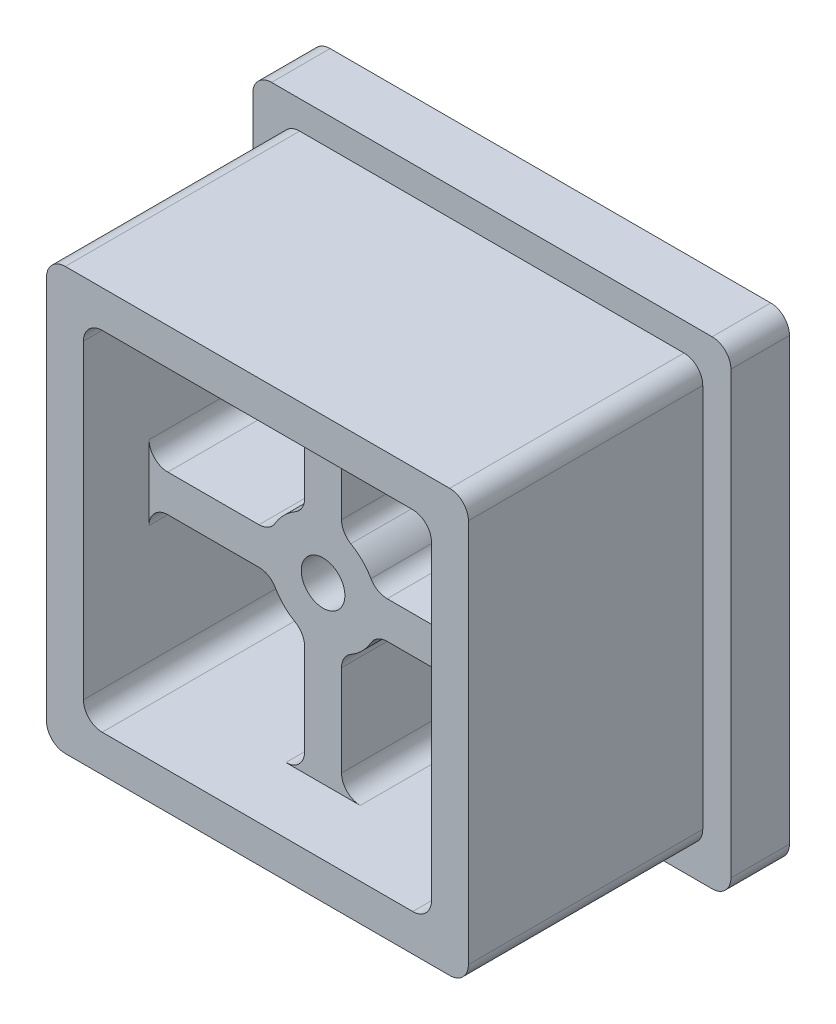
SolidWorks part; units mm, degrees
material "Nylon 101"
ref_plane "Front Plane" through (0, 0, 0) normal (0, 0, 1) x (1, 0, 0)
ref_plane "Top Plane" through (0, 0, 0) normal (0, 1, 0) x (1, 0, 0)
ref_plane "Right Plane" through (0, 0, 0) normal (1, 0, 0) x (0, 0, -1)
sketch "Sketch1" plane through (0, 0, 0) normal (0, 0, 1) x (1, 0, 0)
  line L1 (-5.715, 5.715) -> (5.715, 5.715)
  line L2 (-5.715, 5.715) -> (-5.715, -5.715)
  line L3 (-5.715, -5.715) -> (5.715, -5.715)
  line L4 (5.715, 5.715) -> (5.715, -5.715)
  line L5 (-5.715, 5.715) -> (5.715, -5.715) construction
  line L6 (-5.715, -5.715) -> (5.715, 5.715) construction
  point P0 (0, 0)
  dimension "D1" = 11.43
  dimension "D2" = 11.43
extrude "Boss-Extrude1" add sketch "Sketch1" along normal blind 4.7625 and the other way blind 1.5875
sketch "Sketch2" plane through (0, 0, -1.5875) normal (0, 0, -1) x (-1, 0, 0)
  line L0 (-6.477, 6.477) -> (-6.477, -6.477)
  line L1 (-6.477, -6.477) -> (6.477, -6.477)
  line L2 (6.477, -6.477) -> (6.477, 6.477)
  line L3 (6.477, 6.477) -> (-6.477, 6.477)
  line L4 (-5.715, 5.715) -> (-5.715, -5.715)
  line L5 (-5.715, -5.715) -> (5.715, -5.715)
  line L6 (5.715, -5.715) -> (5.715, 5.715)
  line L7 (5.715, 5.715) -> (-5.715, 5.715)
  line L8 (-5.715, 5.715) -> (-5.715, -5.715) construction
  line L9 (-5.715, -5.715) -> (5.715, -5.715) construction
  line L10 (5.715, -5.715) -> (5.715, 5.715) construction
  line L11 (5.715, 5.715) -> (-5.715, 5.715) construction
  dimension "D1" = 0
  dimension "D2" = 0.762
extrude "Boss-Extrude2" add sketch "Sketch2" along normal blind 1.5875
sketch "Sketch3" plane through (0, 0, 4.7625) normal (0, 0, 1) x (1, 0, 0)
  line L0 (5.207, -5.207) -> (5.207, 5.207)
  line L1 (5.207, 5.207) -> (-5.207, 5.207)
  line L2 (-5.207, 5.207) -> (-5.207, -5.207)
  line L3 (-5.207, -5.207) -> (5.207, -5.207)
  line L4 (5.715, -5.715) -> (5.715, 5.715)
  line L5 (5.715, 5.715) -> (-5.715, 5.715)
  line L6 (-5.715, 5.715) -> (-5.715, -5.715)
  line L7 (-5.715, -5.715) -> (5.715, -5.715)
  line L8 (5.715, -5.715) -> (5.715, 5.715) construction
  line L9 (5.715, 5.715) -> (-5.715, 5.715) construction
  line L10 (-5.715, 5.715) -> (-5.715, -5.715) construction
  line L11 (-5.715, -5.715) -> (5.715, -5.715) construction
  dimension "D1" = 0
  dimension "D2" = 0.508
extrude "Cut-Extrude1" [suppressed] cut sketch "Sketch3" against normal blind 1.8415
sketch "Sketch6" plane through (0, 0, -3.175) normal (0, 0, -1) x (-1, 0, 0)
  line L0 (-6.477, 6.477) -> (6.477, -6.477) construction
  line L2 (1.27, -1.27) -> (-1.27, -1.27)
  line L3 (1.27, -1.27) -> (1.27, 1.27)
  line L4 (1.27, 1.27) -> (-1.27, 1.27)
  line L5 (-1.27, -1.27) -> (-1.27, 1.27)
  line L6 (1.27, -1.27) -> (-1.27, 1.27) construction
  line L7 (1.27, 1.27) -> (-1.27, -1.27) construction
  point P4 (0, 0)
  dimension "D1" = 2.54
  dimension "D2" = 2.54
sketch "Sketch7" [suppressed] plane through (0, 0, 2.921) normal (0, 0, 1) x (1, 0, 0)
  line L0 (7.3025, 7.3025) -> (-7.3025, -7.3025) construction
  line L1 (4.445, -4.445) -> (-4.445, -4.445)
  line L2 (4.445, -4.445) -> (4.445, 4.445)
  line L3 (4.445, 4.445) -> (-4.445, 4.445)
  line L4 (-4.445, -4.445) -> (-4.445, 4.445)
  line L5 (4.445, -4.445) -> (-4.445, 4.445) construction
  line L6 (4.445, 4.445) -> (-4.445, -4.445) construction
  line L7 (-5.207, 5.207) -> (-5.207, -5.207) construction
  line L8 (5.207, 5.207) -> (-5.207, 5.207) construction
  point P0 (0, 0)
  dimension "D1" = 0.762
  dimension "D2" = 0.762
loft "Cut-Loft1" [suppressed] cut profiles "Sketch7", "Sketch6"
fillet "Fillet1" [suppressed] radius 0.508
sketch "Sketch8" [suppressed] plane through (0, 0, 0) normal (1, 0, 0) x (0, 0, -1)
  line L0 (-4.7625, -5.207) -> (-4.7625, -5.715) construction
  line L1 (-4.7625, -5.207) -> (1.5875, -5.207) construction
  line L2 (1.5875, -5.715) -> (-4.7625, -5.715) construction
  line L3 (-4.5085, -5.207) -> (-4.7625, -5.207)
  line L4 (-4.7625, -5.207) -> (-4.7625, -5.715) construction
  line L5 (-4.7625, -5.715) -> (-4.5085, -5.715)
  line L6 (-4.7625, -5.207) -> (-4.7879, -5.207)
  line L7 (-4.7879, -5.207) -> (-4.7879, -5.715)
  line L8 (-4.7879, -5.715) -> (-4.7625, -5.715)
  arc A0 (-4.5085, -5.207) -> (-4.5085, -5.715) centre (-4.5085, -5.461) ccw
  dimension "D1" = 0.0254
sketch "Sketch9" plane through (0, 0, 4.7625) normal (0, 0, 1) x (1, 0, 0)
  line L4 (5.715, 5.715) -> (-5.715, 5.715)
  line L5 (-5.715, 5.715) -> (-5.715, -5.715)
  line L6 (-5.715, -5.715) -> (5.715, -5.715)
  line L7 (5.715, -5.715) -> (5.715, 5.715)
  line L8 (5.715, 5.715) -> (-5.715, 5.715)
  line L9 (-5.715, 5.715) -> (-5.715, -5.715)
  line L10 (-5.715, -5.715) -> (5.715, -5.715)
  line L11 (5.715, -5.715) -> (5.715, 5.715)
  dimension "D1" = 0
sweep "Cut-Sweep2" [suppressed] cut profiles "Sketch8" path "Sketch9"
sketch "Sketch10" [suppressed] plane through (0, 0, 2.921) normal (0, 0, 1) x (1, 0, 0)
  line L0 (-4.3153, 3.8458) -> (-4.3153, -3.8458) construction
  line L1 (-4.3153, -3.8458) -> (-1.27, -0.8005) construction
  line L2 (-1.27, -0.8005) -> (-1.27, 0.8005) construction
  line L3 (-1.27, 0.8005) -> (-4.3153, 3.8458) construction
  line L4 (-0.8005, 1.27) -> (0.8005, 1.27) construction
  line L5 (0.8005, 1.27) -> (3.8458, 4.3153) construction
  line L6 (3.8458, 4.3153) -> (-3.8458, 4.3153) construction
  line L7 (-3.8458, 4.3153) -> (-0.8005, 1.27) construction
  line L8 (1.27, 0.8005) -> (1.27, -0.8005) construction
  line L9 (1.27, -0.8005) -> (4.3153, -3.8458) construction
  line L10 (4.3153, -3.8458) -> (4.3153, 3.8458) construction
  line L11 (4.3153, 3.8458) -> (1.27, 0.8005) construction
  line L12 (0.8005, -1.27) -> (-0.8005, -1.27) construction
  line L13 (-0.8005, -1.27) -> (-3.8458, -4.3153) construction
  line L14 (-3.8458, -4.3153) -> (3.8458, -4.3153) construction
  line L15 (3.8458, -4.3153) -> (0.8005, -1.27) construction
  line L16 (-4.3153, 3.8458) -> (-4.3153, -3.8458) construction
  line L17 (-4.3153, -3.8458) -> (-1.27, -0.8005) construction
  line L18 (-1.27, -0.8005) -> (-1.27, 0.8005) construction
  line L19 (-1.27, 0.8005) -> (-4.3153, 3.8458) construction
  line L20 (-0.8005, 1.27) -> (0.8005, 1.27) construction
  line L21 (0.8005, 1.27) -> (3.8458, 4.3153) construction
  line L22 (3.8458, 4.3153) -> (-3.8458, 4.3153) construction
  line L23 (-3.8458, 4.3153) -> (-0.8005, 1.27) construction
  line L24 (1.27, 0.8005) -> (1.27, -0.8005) construction
  line L25 (1.27, -0.8005) -> (4.3153, -3.8458) construction
  line L26 (4.3153, -3.8458) -> (4.3153, 3.8458) construction
  line L27 (4.3153, 3.8458) -> (1.27, 0.8005) construction
  line L28 (0.8005, -1.27) -> (-0.8005, -1.27) construction
  line L29 (-0.8005, -1.27) -> (-3.8458, -4.3153) construction
  line L30 (-3.8458, -4.3153) -> (3.8458, -4.3153) construction
  line L31 (3.8458, -4.3153) -> (0.8005, -1.27) construction
  line L32 (-3.5533, 2.0061) -> (-3.5533, -2.0061)
  line L33 (-3.5533, -2.0061) -> (-2.032, -0.4849)
  line L34 (-2.032, -0.4849) -> (-2.032, 0.4849)
  line L35 (-2.032, 0.4849) -> (-3.5533, 2.0061)
  line L36 (-0.4849, 2.032) -> (0.4849, 2.032)
  line L37 (0.4849, 2.032) -> (2.0061, 3.5533)
  line L38 (2.0061, 3.5533) -> (-2.0061, 3.5533)
  line L39 (-2.0061, 3.5533) -> (-0.4849, 2.032)
  line L40 (2.032, 0.4849) -> (2.032, -0.4849)
  line L41 (2.032, -0.4849) -> (3.5533, -2.0061)
  line L42 (3.5533, -2.0061) -> (3.5533, 2.0061)
  line L43 (3.5533, 2.0061) -> (2.032, 0.4849)
  line L44 (0.4849, -2.032) -> (-0.4849, -2.032)
  line L45 (-0.4849, -2.032) -> (-2.0061, -3.5533)
  line L46 (-2.0061, -3.5533) -> (2.0061, -3.5533)
  line L47 (2.0061, -3.5533) -> (0.4849, -2.032)
  dimension "D1" = 0.762
extrude "Cut-Extrude2" [suppressed] cut sketch "Sketch10" against normal offset from surface (6.4135 mm away) 1.27 up to face at (0, 0, -3.175)
fillet "Fillet4" [suppressed] radius 0.254
fillet "Fillet5" [suppressed] radius 0.254
sketch "Sketch11" [suppressed] plane through (0, 0, 2.921) normal (0, 0, 1) x (1, 0, 0)
  line L1 (2.54, -2.54) -> (-2.54, -2.54)
  line L2 (2.54, -2.54) -> (2.54, 2.54)
  line L3 (2.54, 2.54) -> (-2.54, 2.54)
  line L4 (-2.54, -2.54) -> (-2.54, 2.54)
  line L5 (2.54, -2.54) -> (-2.54, 2.54) construction
  line L6 (2.54, 2.54) -> (-2.54, -2.54) construction
  point P0 (0, 0)
  dimension "D1" = 5.08
  dimension "D2" = 5.08
extrude "Cut-Extrude3" [suppressed] cut sketch "Sketch11" against normal through all draft 5
sketch "Sketch12" [suppressed] plane through (0, 0, 2.921) normal (0, 0, 1) x (1, 0, 0)
  line L0 (-5.207, 0) -> (5.207, 0)
  line L1 (-5.207, 5.207) -> (-5.207, -5.207) construction
  line L2 (5.207, -5.207) -> (5.207, 5.207) construction
  line L3 (0, 5.207) -> (0, -5.207)
  line L4 (5.207, 5.207) -> (-5.207, 5.207) construction
  line L5 (-5.207, -5.207) -> (5.207, -5.207) construction
extrude "Cut-Extrude-Thin1" [suppressed] cut sketch "Sketch12" against normal offset from surface (6.4135 mm away) 1.27 thin up to face at (0, 0, -3.175) thin type mid plane wall 7.62
fillet "Fillet6" [suppressed] radius 0.508
sketch "Sketch13" [suppressed] plane through (0, 0, 0) normal (1, 0, 0) x (0, 0, -1)
  line L0 (1.5875, -5.715) -> (-4.7625, -5.715) construction
  line L1 (-2.921, -5.207) -> (-4.7625, -5.207) construction
  line L2 (-4.7625, -5.715) -> (-4.7625, 5.715) construction
  line L3 (-4.5085, -5.207) -> (-5.0165, -5.207)
  line L4 (-5.0165, -5.207) -> (-5.0165, -5.715)
  line L5 (-5.0165, -5.715) -> (-4.5085, -5.715)
  arc A0 (-4.5085, -5.207) -> (-4.5085, -5.715) centre (-4.5085, -5.461) ccw
  dimension "D1" = 0.508
sketch "Sketch14" plane through (0, 0, 4.7625) normal (0, 0, 1) x (1, 0, 0)
  line L4 (5.715, -5.715) -> (5.715, 5.715)
  line L5 (5.715, 5.715) -> (-5.715, 5.715)
  line L6 (-5.715, 5.715) -> (-5.715, -5.715)
  line L7 (-5.715, -5.715) -> (5.715, -5.715)
  line L8 (5.715, -5.715) -> (5.715, 5.715)
  line L9 (5.715, 5.715) -> (-5.715, 5.715)
  line L10 (-5.715, 5.715) -> (-5.715, -5.715)
  line L11 (-5.715, -5.715) -> (5.715, -5.715)
  dimension "D1" = 0
sweep "Cut-Sweep3" [suppressed] cut profiles "Sketch13" path "Sketch14"
shell "Shell1" thickness 1 removed face at (0, 0, -3.175) removed face at (0, 0, 4.7625)
sketch "Sketch15" plane through (0, 0, -3.175) normal (0, 0, -1) x (-1, 0, 0)
  circle A0 centre (0, 0) radius 1.5
  dimension "D1" = 3
extrude "Boss-Extrude3" add sketch "Sketch15" against normal offset from surface (6.1595 mm away) 1.778 separate body up to face at (0, 0, 4.7625)
sketch "Sketch16" plane through (0, 0, 2.9845) normal (0, 0, 1) x (1, 0, 0)
  line L0 (0, 4.715) -> (0, -4.715)
  line L1 (4.715, 4.715) -> (-4.715, 4.715) construction
  line L2 (-4.715, -4.715) -> (4.715, -4.715) construction
  line L4 (4.715, -4.715) -> (4.715, 4.715) construction
  line L5 (4.715, 0) -> (-4.715, 0)
  line L6 (-4.715, 4.715) -> (-4.715, -4.715) construction
extrude "Extrude-Thin1" add sketch "Sketch16" against normal up to surface (6.1595 mm away) thin up to face at (0, 0, -3.175) thin type mid plane wall 1
sketch "Sketch17" plane through (0, 0, -3.175) normal (0, 0, -1) x (-1, 0, 0)
  line L1 (4.715, 4.715) -> (-4.715, 4.715)
  line L2 (-4.715, 4.715) -> (-4.715, -4.715)
  line L3 (-4.715, -4.715) -> (4.715, -4.715)
  line L4 (4.715, -4.715) -> (4.715, 4.715)
  line L5 (5.477, 5.477) -> (-5.477, 5.477)
  line L6 (-5.477, 5.477) -> (-5.477, -5.477)
  line L8 (-5.477, -5.477) -> (5.477, -5.477)
  line L9 (5.477, -5.477) -> (5.477, 5.477)
  line L10 (5.477, 5.477) -> (-5.477, 5.477)
  line L11 (-5.477, 5.477) -> (-5.477, -5.477)
  line L12 (-5.477, -5.477) -> (5.477, -5.477)
  line L13 (5.477, -5.477) -> (5.477, 5.477)
  dimension "D1" = 0
  dimension "D2" = 0.762
extrude "Boss-Extrude4" add sketch "Sketch17" against normal up to next
sketch "Sketch18" plane through (0, 0, 2.9845) normal (0, 0, 1) x (1, 0, 0)
  circle A0 centre (0, 0) radius 0.5
  arc A3 (0.5, -1.4142) -> (1.4142, -0.5) centre (0, 0) ccw construction
  dimension "D1" = 1
extrude "Cut-Extrude4" [suppressed] cut sketch "Sketch18" against normal through all
fillet "Fillet7" radius 0.508 8 edges at (-6.477, -6.477, -2.3812) (-5.715, -5.715, 1.5875) (5.715, -5.715, 1.5875) (6.477, -6.477, -2.3812) (5.715, 5.715, 1.5875) (6.477, 6.477, -2.3812) (-6.477, 6.477, -2.3812) (-5.715, 5.715, 1.5875)
fillet "Fillet8" radius 0.508 20 edges at (-4.715, -4.715, 0.7938) (-4.715, 4.715, 0.7938) (4.715, 4.715, 0.7938) (4.715, -4.715, 0.7938) (-0.5, 4.715, -0.0952) (0.5, 4.715, -0.0952) (4.715, 0.5, -0.0952) (4.715, -0.5, -0.0953) (0.5, -4.715, -0.0952) (-0.5, -4.715, -0.0952) (-4.715, -0.5, -0.0952) (-4.715, 0.5, -0.0952) (-1.4142, -0.5, -0.0953) (-0.5, -1.4142, -0.0953) (0.5, -1.4142, -0.0952) (1.4142, -0.5, -0.0952) (1.4142, 0.5, -0.0953) (0.5, 1.4142, -0.0952) (-0.5, 1.4142, -0.0953) (-1.4142, 0.5, -0.0952)
sketch "Sketch20" plane through (0, 0, -3.175) normal (0, 0, -1) x (-1, 0, 0)
  circle A0 centre (0, 0) radius 0.635
  dimension "D1" = 1.27
split line "Split Line1" [suppressed]
dome "Dome2" [suppressed] faces to dome 1 distance 0.635 parameters "D1"=0.635
hole_wizard "#56 (0.0465) Diameter Hole1" positions "Sketch22" profile "Sketch21" hole size "#56" standard "ANSI Inch" end condition through all
sketch "Sketch22" plane through (0, 0, 2.9845) normal (0, 0, 1) x (1, 0, 0)
  point P0 (0, 0)
sketch "Sketch21" plane through (0, 0, 2.9845) normal (1, 0, 0) x (0, -1, 0)
  line L0 (0, 0) -> (0, 6.1595)
  line L1 (0, 6.1595) -> (0.5905, 6.1595)
  line L2 (0.5905, 6.1595) -> (0.5905, 0)
  line L5 (0.5905, 0) -> (0, 0)
  line L11 (0, -6.35) -> (0, 107.95) construction
  dimension "Thru Hole Dia." = 1.1811
  dimension "Thru Hole Depth" = 6.1595
equation "\"D2@Sketch7\"=\"D1@Sketch7\""
